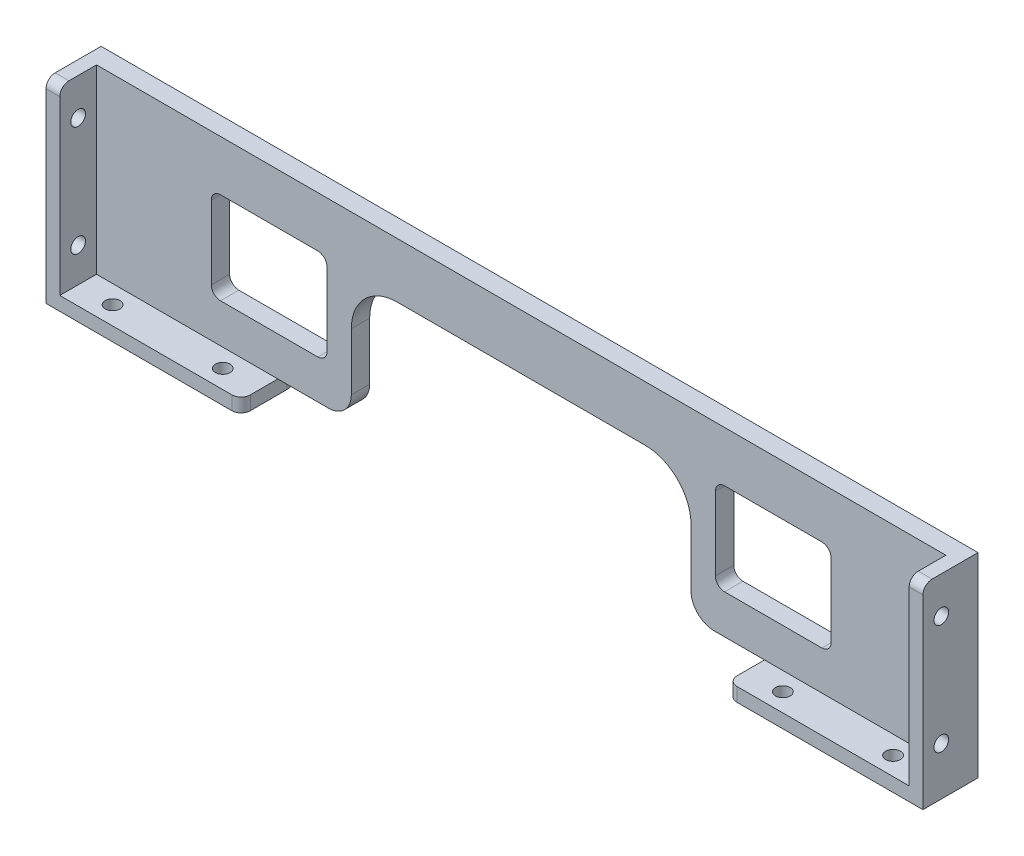
SolidWorks part; units mm, degrees
ref_plane "前视基准面" through (0, 0, 0) normal (0, 0, 1) x (1, 0, 0)
ref_plane "上视基准面" through (0, 0, 0) normal (0, 1, 0) x (1, 0, 0)
ref_plane "右视基准面" through (0, 0, 0) normal (1, 0, 0) x (0, 0, -1)
other "Configuration Table"
sketch "草图1" plane through (0, 0, 0) normal (0, 0, 1) x (1, 0, 0)
  line L0 (0, 0) -> (0, 42.5)
  line L1 (0, 42.5) -> (3, 42.5)
  line L2 (3, 42.5) -> (3, 3)
  line L3 (3, 3) -> (42.5, 3)
  line L4 (42.5, 3) -> (42.5, 0)
  line L5 (42.5, 0) -> (0, 0)
  line L6 (58.5, 20.5) -> (58.5, 8)
  line L10 (0, 0) -> (3, 3) construction
  line L16 (3, 42.5) -> (95.5, 42.5)
  line L18 (30, 31.5) -> (42, 31.5)
  line L19 (44, 29.5) -> (44, 13.5)
  line L20 (68.5, 30.5) -> (95.5, 30.5)
  line L21 (42, 11.5) -> (30, 11.5)
  line L22 (28, 13.5) -> (28, 29.5)
  line L23 (95.5, 30.5) -> (95.5, 42.5)
  line L24 (53.5, 3) -> (42.5, 3)
  arc A10 (42, 31.5) -> (44, 29.5) centre (42, 29.5) cw
  arc A11 (44, 13.5) -> (42, 11.5) centre (42, 13.5) cw
  arc A12 (30, 11.5) -> (28, 13.5) centre (30, 13.5) cw
  arc A13 (30, 31.5) -> (28, 29.5) centre (30, 29.5) ccw
  arc A14 (58.5, 20.5) -> (68.5, 30.5) centre (68.5, 20.5) cw
  arc A15 (58.5, 8) -> (53.5, 3) centre (53.5, 8) cw
  point P5 (36, 31.5)
  point P14 (28, 21.5)
  point P29 (58.5, 3)
  dimension "D5" = 53
  dimension "D6" = 2
  dimension "D7" = 20
  dimension "D8" = 33
  dimension "D9" = 16
  dimension "D10" = 12
  dimension "D11" = 10
  dimension "D13" = 5
  dimension "D1" = 42.5
  dimension "D2" = 42.5
  dimension "D3" = 3
  dimension "D4" = 3
  dimension "D12" = 16
  dimension "D14" = 21
extrude "凸台-拉伸1" add sketch "草图1" along normal blind 12 contours L5 L4 L3 L2 L1 L0 | L5 L0 L1 L2 L3 L4 region at (0.601, 21.25, 0)
extrude "凸台-拉伸2" add sketch "草图1<6>" along normal blind 4 contours L16 L2 L3 A13 L18 A10 L19 A11 L21 A12 L22 region at (49.25, 41.4942, 0)
sketch "草图1<6>" plane through (0, 0, 0) normal (0, 0, 1) x (1, 0, 0) same geometry as "草图1"
sketch "草图3" plane through (0, 0, 0) normal (-1, 0, 0) x (0, 0, 1)
  line L0 (0, 0) -> (8, 0) construction
  line L1 (12, 0) -> (0, 0) construction
  circle A0 centre (8, 10.5) radius 1.6
  circle A1 centre (8, 34.5) radius 1.6
  dimension "D2" = 3.2
  dimension "D3" = 3.2
  dimension "D1" = 8
  dimension "D4" = 10.5
  dimension "D5" = 24
sketch "草图4" plane through (0, 0, 0) normal (0, -1, 0) x (1, 0, 0)
  line L0 (0, 0) -> (0, 8) construction
  line L1 (0, 9.6) -> (0, 6.4) construction
  line L2 (0, 0) -> (0, 8) construction
  circle A0 centre (10.5, 8) radius 1.6
  circle A1 centre (34.5, 8) radius 1.6
  dimension "D2" = 3.2
  dimension "D1" = 8
  dimension "D3" = 10.5
  dimension "D4" = 24
extrude "切除-拉伸1" cut sketch "草图3" against normal up to next
extrude "切除-拉伸2" cut sketch "草图4" against normal up to next
fillet "圆角2" radius 2 3 edges at (1.5, 42.5, 12) (42.5, 1.5, 0) (42.5, 1.5, 12)
mirror "镜向1" about plane through (95.5, 0, 4) normal (-1, 0, 0) of bodies 110
sketch "草图5" plane through (0, 0, 4) normal (0, 0, 1) x (1, 0, 0)
  line L0 (42, 11.5) -> (30, 11.5) construction
  line L1 (42, 31.5) -> (53.2, 31.5)
  line L2 (42, 31.5) -> (42, 11.5)
  line L3 (42, 11.5) -> (53.2, 11.5)
  line L4 (53.2, 31.5) -> (53.2, 11.5)
  line L5 (28, 13.5) -> (28, 29.5) construction
  line L6 (163, 13.5) -> (163, 29.5) construction
  line L7 (149, 31.5) -> (137.8, 31.5)
  line L8 (149, 31.5) -> (149, 11.5)
  line L9 (149, 11.5) -> (137.8, 11.5)
  line L10 (137.8, 31.5) -> (137.8, 11.5)
  dimension "D1" = 25.2
  dimension "D2" = 20
  dimension "D3" = 25.2
extrude "切除-拉伸3" cut sketch "草图5" against normal blind 20 contours L2 L1 L4 L3 | L8 L7 L10 L9
fillet "圆角4" radius 2 4 edges at (137.8, 31.5, 2) (137.8, 11.5, 2) (53.2, 11.5, 2) (53.2, 31.5, 2)
